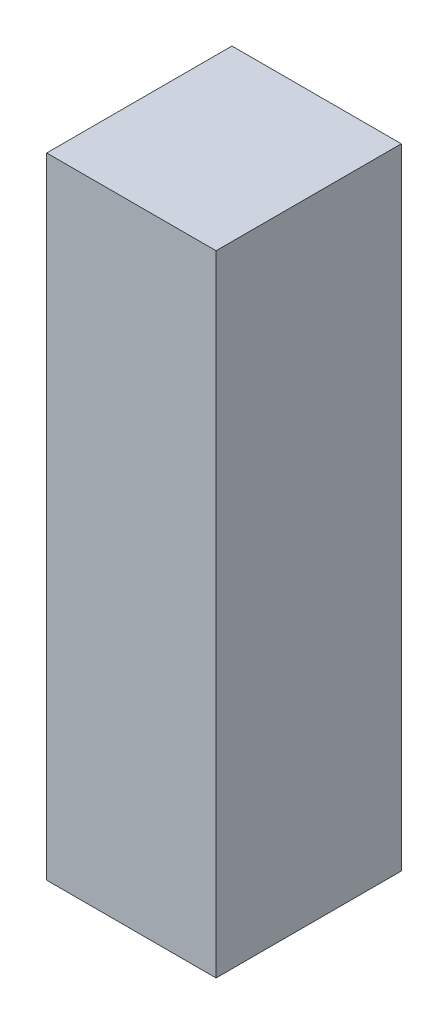
SolidWorks part; units mm, degrees
ref_plane "Front Plane" through (0, 0, 0) normal (0, 0, 1) x (1, 0, 0)
ref_plane "Top Plane" through (0, 0, 0) normal (0, 1, 0) x (1, 0, 0)
ref_plane "Right Plane" through (0, 0, 0) normal (1, 0, 0) x (0, 0, -1)
sketch "Sketch1" plane through (0, 0, 0) normal (0, 1, 0) x (1, 0, 0)
  line L1 (0, 0) -> (32, 0)
  line L2 (0, 0) -> (0, 35)
  line L3 (0, 35) -> (32, 35)
  line L4 (32, 0) -> (32, 35)
  dimension "D1" = 32
  dimension "D2" = 35
extrude "Boss-Extrude1" add sketch "Sketch1" along normal blind 119
